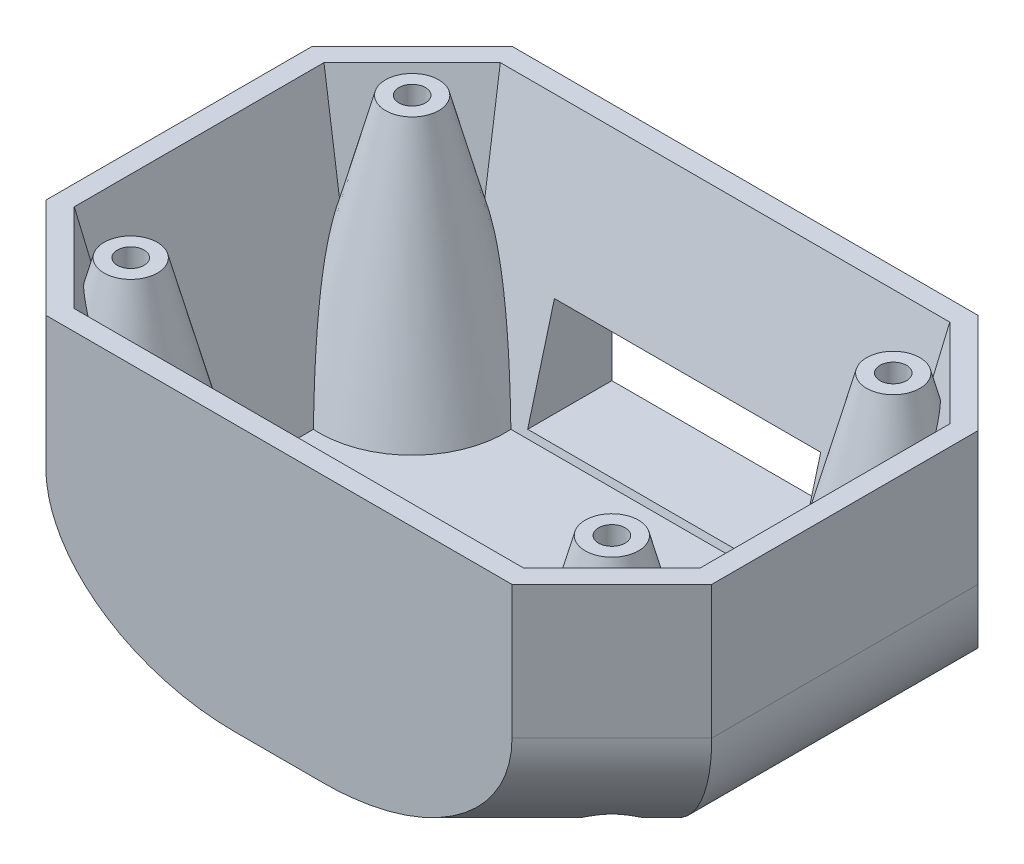
SolidWorks part; units mm, degrees
ref_plane "Front Plane" through (0, 0, 0) normal (0, 0, 1) x (1, 0, 0)
ref_plane "Top Plane" through (0, 0, 0) normal (0, 1, 0) x (1, 0, 0)
ref_plane "Right Plane" through (0, 0, 0) normal (1, 0, 0) x (0, 0, -1)
sketch "Sketch1" plane through (0, 0, 0) normal (0, 1, 0) x (1, 0, 0)
  line L6 (63.5, 88.9) -> (63.5, 0) construction
  line L7 (0, 0) -> (127, 0) construction
  line L8 (0, 0) -> (0, 88.9) construction
  line L9 (0, 88.9) -> (127, 88.9) construction
  line L10 (127, 0) -> (127, 88.9) construction
  line L11 (127, 44.45) -> (0, 44.45) construction
  line L12 (107.95, 88.9) -> (19.05, 88.9)
  line L13 (19.05, 88.9) -> (0, 69.85)
  line L14 (0, 69.85) -> (0, 19.05)
  line L15 (19.05, 0) -> (0, 19.05)
  line L16 (107.95, 0) -> (19.05, 0)
  line L17 (107.95, 0) -> (127, 19.05)
  line L18 (127, 69.85) -> (127, 19.05)
  line L19 (107.95, 88.9) -> (127, 69.85)
  dimension "D1" = 45
  dimension "D2" = 19.05
  dimension "D3" = 127
  dimension "D4" = 88.9
extrude "Boss-Extrude1" add sketch "Sketch1" along normal blind 50.8
fillet "Fillet1" radius 25.4 4 edges at (0, 0, -44.45) (9.525, 0, -9.525) (117.475, 0, -9.525) (127, 0, -44.45)
sketch "Sketch2" plane through (0, 50.8, 0) normal (0, 1, 0) x (1, 0, 0)
  line L0 (17.6072, 71.2928) -> (12.2191, 76.6809) construction
  line L9 (107.95, 88.9) -> (19.05, 88.9) construction
  line L11 (63.5, 85.09) -> (63.5, 88.9) construction
  line L12 (12.2191, 76.6809) -> (9.525, 79.375) construction
  line L13 (19.05, 88.9) -> (0, 69.85) construction
  line L14 (0, 69.85) -> (0, 19.05) construction
  line L15 (0, 19.05) -> (19.05, 0) construction
  line L16 (19.05, 0) -> (107.95, 0) construction
  line L17 (107.95, 0) -> (127, 19.05) construction
  line L18 (127, 19.05) -> (127, 69.85) construction
  line L19 (3.81, 44.45) -> (0, 44.45) construction
  line L20 (63.5, 3.81) -> (63.5, 0) construction
  line L21 (123.19, 44.45) -> (127, 44.45) construction
  line L36 (63.5, 85.09) -> (63.5, 3.81) construction
  line L37 (3.81, 44.45) -> (123.19, 44.45) construction
  line L52 (106.3718, 85.09) -> (20.6282, 85.09)
  line L53 (123.19, 68.2718) -> (106.3718, 85.09)
  line L54 (123.19, 20.6282) -> (123.19, 68.2718)
  line L55 (106.3718, 3.81) -> (123.19, 20.6282)
  line L56 (20.6282, 3.81) -> (106.3718, 3.81)
  line L57 (3.81, 20.6282) -> (20.6282, 3.81)
  line L58 (3.81, 68.2718) -> (3.81, 20.6282)
  line L59 (20.6282, 85.09) -> (3.81, 68.2718)
  circle A0 centre (17.6072, 71.2928) radius 5.08
  circle A1 centre (17.6072, 71.2928) radius 2.54
  circle A2 centre (17.6072, 17.6072) radius 2.54
  circle A3 centre (17.6072, 17.6072) radius 5.08
  circle A4 centre (109.3928, 17.6072) radius 2.54
  circle A5 centre (109.3928, 17.6072) radius 5.08
  circle A6 centre (109.3928, 71.2928) radius 2.54
  circle A7 centre (109.3928, 71.2928) radius 5.08
  dimension "D3" = 5.08
  dimension "D4" = 7.62
  dimension "D1" = 3.81
  dimension "D2" = 2.54
extrude "Cut-Extrude8" cut sketch "Sketch2" against normal blind 46.99 draft 15 contours L52 L59 L58 L57 L56 L55 L54 L53 A5 A0 A3 A7 region at (63.5, 50.8, -44.45)
extrude "Cut-Extrude10" cut sketch "Sketch2<5>" against normal blind 25.4 contours A1 | A2 | A6 | A4 region at (17.6072, 50.8, -71.2928) region at (17.6072, 50.8, -17.6072) region at (109.3928, 50.8, -71.2928)
sketch "Sketch2<5>" plane through (0, 50.8, 0) normal (0, 1, 0) x (1, 0, 0) same geometry as "Sketch2"
ref_plane "Plane1" through (0, 25.4, 0) normal (0, -1, 0) x (-1, 0, 0)
sketch "Sketch4" plane through (0, 25.4, 0) normal (0, -1, 0) x (-1, 0, 0)
  circle A0 centre (-109.3928, 71.2928) radius 4.445
  circle A1 centre (-109.3928, 17.6072) radius 4.445
  circle A2 centre (-17.6072, 17.6072) radius 4.445
  circle A3 centre (-17.6072, 71.2928) radius 4.445
  dimension "D1" = 8.89
extrude "Cut-Extrude11" cut sketch "Sketch4" along normal blind 25.4
sketch "Sketch5" plane through (0, 0, -88.9) normal (0, 0, -1) x (-1, 0, 0)
  line L1 (-107.95, 50.8) -> (-19.05, 50.8) construction
  line L2 (-88.9, 5.08) -> (-38.1, 5.08)
  line L4 (-88.9, 5.08) -> (-88.9, 24.13)
  line L5 (-88.9, 24.13) -> (-38.1, 24.13)
  line L6 (-38.1, 5.08) -> (-38.1, 24.13)
  line L7 (-101.6, 0) -> (-25.4, 0) construction
  point P4 (-63.5, 24.13)
  point P7 (-63.5, 50.8)
  dimension "D2" = 50.8
  dimension "D1" = 19.05
  dimension "D3" = 5.08
extrude "Cut-Extrude12" cut sketch "Sketch5" against normal up to next
